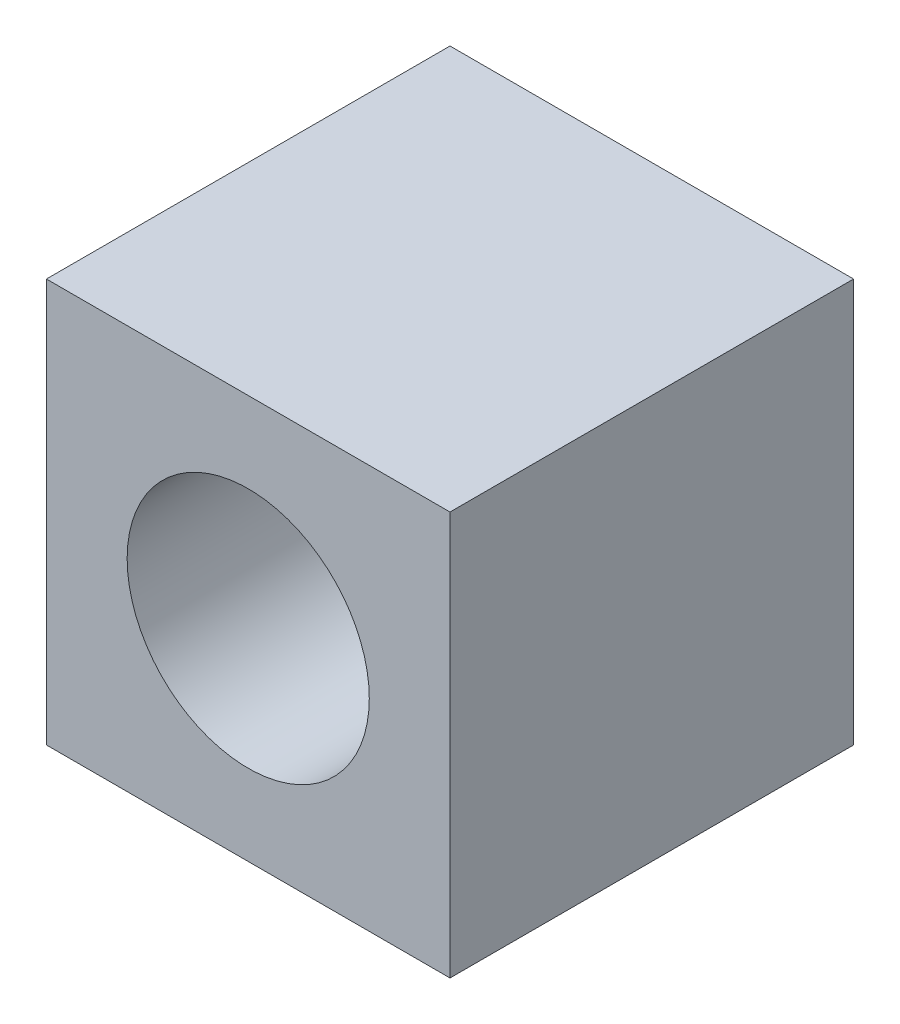
SolidWorks part; units mm, degrees
ref_plane "Alzado" through (0, 0, 0) normal (0, 0, 1) x (1, 0, 0)
ref_plane "Planta" through (0, 0, 0) normal (0, 1, 0) x (1, 0, 0)
ref_plane "Vista lateral" through (0, 0, 0) normal (1, 0, 0) x (0, 0, -1)
sketch "Croquis1" plane through (0, 0, 0) normal (0, 0, 1) x (1, 0, 0)
  line L1 (-50, -50) -> (50, -50)
  line L2 (-50, -50) -> (-50, 50)
  line L3 (-50, 50) -> (50, 50)
  line L4 (50, -50) -> (50, 50)
  line L5 (-50, -50) -> (50, 50) construction
  line L6 (-50, 50) -> (50, -50) construction
  point P0 (0, 0)
  dimension "D1" = 100
  dimension "D2" = 100
extrude "Saliente-Extruir1" add sketch "Croquis1" along normal blind 100
sketch "Croquis2" plane through (0, 0, 100) normal (0, 0, 1) x (1, 0, 0)
  circle A0 centre (0, 0) radius 30
  dimension "D1" = 60
extrude "Cortar-Extruir1" cut sketch "Croquis2" against normal through all
